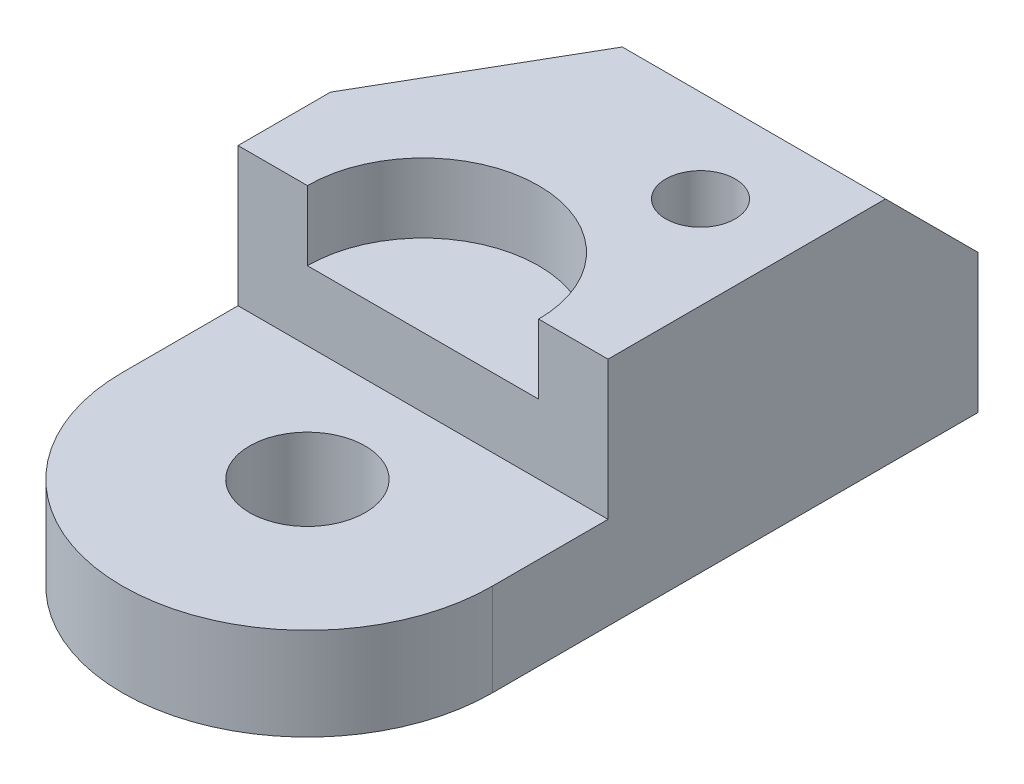
SolidWorks part; units mm, degrees
material "AISI 316 Stainless Steel Sheet (SS)"
ref_plane "Front Plane" through (0, 0, 0) normal (0, 0, 1) x (1, 0, 0)
ref_plane "Top Plane" through (0, 0, 0) normal (0, 1, 0) x (1, 0, 0)
ref_plane "Right Plane" through (0, 0, 0) normal (1, 0, 0) x (0, 0, -1)
ref_axis "X-axis" through (-88.99, 0, 0) along (1, 0, 0)
ref_axis "Y-axis" through (0, 55, 0) along (0, -1, 0)
ref_axis "Z-axis" through (0, 0, -88.99) along (0, 0, 1)
sketch "Sketch1" plane through (0, 0, 0) normal (0, 1, 0) x (1, 0, 0)
  line L0 (-50.8, 0) -> (50.8, 0)
  line L1 (-50.8, 0) -> (-50.8, -31.75)
  line L2 (50.8, 0) -> (50.8, -31.75)
  line L3 (-50.8, 0) -> (-50.8, 25.4)
  line L4 (-50.8, 25.4) -> (-6.8059, 101.6)
  line L5 (-6.8059, 101.6) -> (50.8, 101.6)
  line L6 (50.8, 101.6) -> (50.8, 0)
  line L7 (-50.8, 25.4) -> (-50.8, 133.8935) construction
  line L8 (-50.8, 0) -> (50.8, 0)
  line L9 (-50.8, 0) -> (50.8, 0)
  line L10 (-50.8, 25.4) -> (-50.8, 0)
  line L11 (50.8, 0) -> (50.8, 101.6)
  arc A0 (-50.8, -31.75) -> (50.8, -31.75) centre (0, -31.75) ccw
  point P4 (0, 0)
  dimension "D1" = 50.8
  dimension "D2" = 133.35
  dimension "D3" = 101.6
  dimension "D4" = 30
  dimension "D5" = 25.4
  dimension "D6" = 101.6
extrude "Boss-Extrude1" add sketch "Sketch1" along normal blind 25.4 contours L1 A0 L2 L0 region at (0, 0, 36.7213)
sketch "Sketch2" plane through (0, 0, 0) normal (0, 1, 0) x (1, 0, 0)
  line L0 (-50.8, 0) -> (-50.8, 25.4)
  line L1 (-50.8, 25.4) -> (-6.8059, 101.6)
  line L2 (-6.8059, 101.6) -> (50.8, 101.6)
  line L3 (50.8, 101.6) -> (50.8, 0)
  line L4 (50.8, 0) -> (-50.8, 0)
  line L5 (-50.8, 25.4) -> (-50.8, 126.5586) construction
  dimension "D1" = 25.4
  dimension "D2" = 101.6
  dimension "D3" = 30
extrude "Boss-Extrude2" add sketch "Sketch2" along normal blind 63.5
sketch "Sketch3" plane through (0, 0, 0) normal (1, 0, 0) x (0, 0, -1)
  line L0 (76.2, 63.5) -> (101.6, 63.5)
  line L1 (0, 63.5) -> (101.6, 63.5) construction
  line L2 (101.6, 63.5) -> (101.6, 38.1)
  line L3 (101.6, 63.5) -> (101.6, 0) construction
  line L4 (101.6, 38.1) -> (76.2, 63.5)
  dimension "D1" = 45
  dimension "D2" = 25.4
extrude "Cut-Extrude1" cut sketch "Sketch3" against normal through all both and the other way through all
hole_wizard "1/4 (0.75) Diameter Hole1" positions "Sketch4" profile "Sketch5" hole size "1/4" standard "ANSI Inch" end condition through all
sketch "Sketch4" plane through (0, 63.5, 0) normal (0, 1, 0) x (1, 0, 0)
  line L0 (50.8, 0) -> (50.8, 76.2) construction
  line L1 (-6.8059, 101.6) -> (50.8, 101.6) construction
  point P0 (25.4, 50.8)
  dimension "D1" = 25.4
  dimension "D2" = 50.8
sketch "Sketch5" plane through (25.4, 63.5, -50.8) normal (1, 0, 0) x (0, 0, 1)
  line L0 (0, 0) -> (0, 63.5)
  line L1 (0, 63.5) -> (9.525, 63.5)
  line L2 (9.525, 63.5) -> (9.525, 0)
  line L5 (9.525, 0) -> (0, 0)
  line L11 (0, -6.35) -> (0, 107.95) construction
  dimension "Thru Hole Dia." = 19.05
  dimension "Thru Hole Depth" = 63.5
sketch "Sketch6" plane through (0, 63.5, 0) normal (0, 1, 0) x (1, 0, 0)
  circle A0 centre (0, 0) radius 31.75
  dimension "D1" = 63.5
extrude "Cut-Extrude2" cut sketch "Sketch6" against normal blind 19.05
hole_wizard "1/4 (1.25) Diameter Hole1" positions "Sketch7" profile "Sketch8" hole size "1/4" standard "ANSI Inch" end condition through all
sketch "Sketch7" plane through (0, 25.4, 0) normal (0, 1, 0) x (1, 0, 0)
  point P0 (0, -31.75)
sketch "Sketch8" plane through (0, 25.4, 31.75) normal (1, 0, 0) x (0, 0, 1)
  line L0 (0, 0) -> (0, 25.4)
  line L1 (0, 25.4) -> (15.875, 25.4)
  line L2 (15.875, 25.4) -> (15.875, 0)
  line L5 (15.875, 0) -> (0, 0)
  line L11 (0, -6.35) -> (0, 107.95) construction
  dimension "Thru Hole Dia." = 31.75
  dimension "Thru Hole Depth" = 25.4
